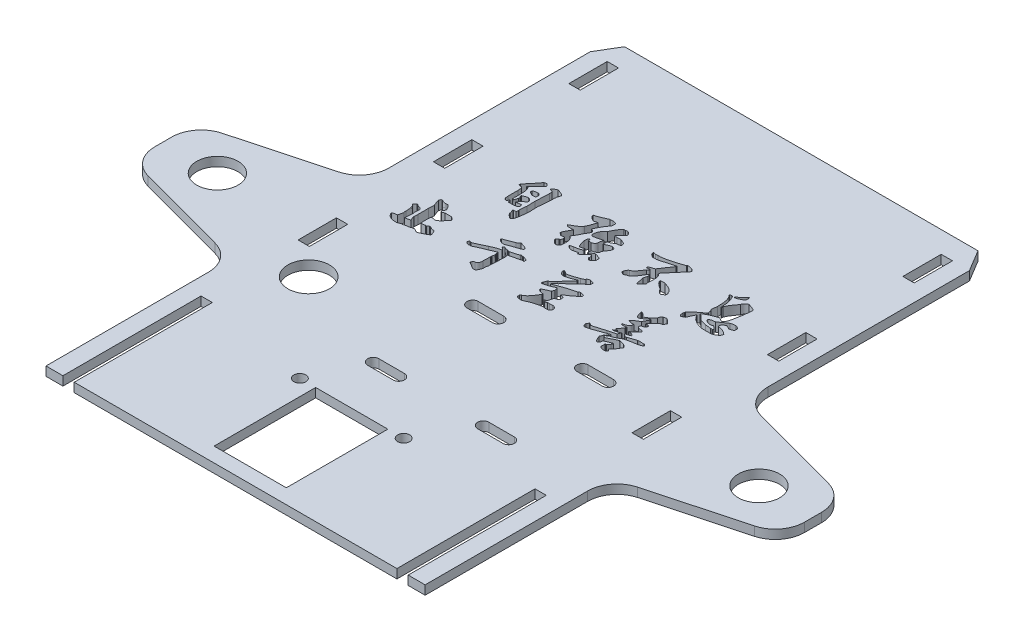
SolidWorks part; units mm, degrees
ref_plane "前视基准面" through (0, 0, 0) normal (0, 0, 1) x (1, 0, 0)
ref_plane "上视基准面" through (0, 0, 0) normal (0, 1, 0) x (1, 0, 0)
ref_plane "右视基准面" through (0, 0, 0) normal (1, 0, 0) x (0, 0, -1)
sketch "草图2" plane through (0, 0, 0) normal (0, 1, 0) x (1, 0, 0)
  line L0 (0, 0) -> (176.8067, 0) construction
  line L1 (-38.25, 19.425) -> (-38.25, 27.925)
  line L2 (-42, 62.675) -> (42, 62.675)
  line L3 (42, 62.675) -> (42, -62.675)
  line L4 (42, -62.675) -> (-42, -62.675) construction
  line L5 (-42, -62.675) -> (-42, 62.675)
  line L14 (0, 0) -> (0, 100.3728) construction
  line L15 (35.75, 57.925) -> (38.25, 57.925)
  line L16 (38.25, 57.925) -> (38.25, 49.425)
  line L17 (38.25, 49.425) -> (35.75, 49.425)
  line L18 (35.75, 49.425) -> (35.75, 57.925)
  line L19 (-38.25, 49.425) -> (-38.25, 57.925)
  line L20 (-38.25, 57.925) -> (-35.75, 57.925)
  line L21 (-35.75, 57.925) -> (-35.75, 49.425)
  line L22 (-35.75, 49.425) -> (-38.25, 49.425)
  line L23 (-38.25, 27.925) -> (-35.75, 27.925)
  line L24 (-35.75, 27.925) -> (-35.75, 19.425)
  line L25 (-35.75, 19.425) -> (-38.25, 19.425)
  line L26 (35.75, 27.925) -> (38.25, 27.925)
  line L27 (38.25, 27.925) -> (38.25, 19.425)
  line L28 (38.25, 19.425) -> (35.75, 19.425)
  line L29 (35.75, 19.425) -> (35.75, 27.925)
  line L30 (-38.25, -10.575) -> (-38.25, -2.075)
  line L31 (-38.25, -2.075) -> (-35.75, -2.075)
  line L32 (-35.75, -2.075) -> (-35.75, -10.575)
  line L33 (-35.75, -10.575) -> (-38.25, -10.575)
  line L34 (35.75, -2.075) -> (38.25, -2.075)
  line L35 (38.25, -2.075) -> (38.25, -10.575)
  line L36 (38.25, -10.575) -> (35.75, -10.575)
  line L37 (35.75, -10.575) -> (35.75, -2.075)
  line L38 (-38.25, -40.575) -> (-38.25, -32.075)
  line L39 (-38.25, -32.075) -> (-35.75, -32.075)
  line L40 (-35.75, -32.075) -> (-35.75, -40.575)
  line L41 (-35.75, -40.575) -> (-38.25, -40.575) construction
  line L42 (35.75, -32.075) -> (38.25, -32.075)
  line L43 (38.25, -32.075) -> (38.25, -40.575)
  line L44 (38.25, -40.575) -> (35.75, -40.575) construction
  line L45 (35.75, -40.575) -> (35.75, -32.075)
  line L46 (-38.25, -40.575) -> (-38.25, -60.625)
  line L47 (-38.25, -60.625) -> (-35.75, -60.625) construction
  line L48 (-35.75, -60.625) -> (-35.75, -40.575)
  line L49 (38.25, -60.625) -> (35.75, -60.625) construction
  line L50 (35.75, -40.575) -> (35.75, -60.625)
  line L51 (38.25, -40.575) -> (38.25, -60.625)
  line L52 (-38.25, -60.625) -> (-38.25, -62.675)
  line L53 (-38.25, -62.675) -> (-42, -62.675)
  line L54 (-35.75, -60.625) -> (-35.75, -62.675)
  line L55 (-35.75, -62.675) -> (35.75, -62.675)
  line L56 (35.75, -62.675) -> (35.75, -60.625)
  line L57 (38.25, -60.625) -> (38.25, -62.675)
  line L58 (38.25, -62.675) -> (42, -62.675)
  dimension "D1" = 71.5
  dimension "D2" = 2.5
  dimension "D3" = 4.75
  dimension "D4" = 8.5
  dimension "D6" = 125.35
  dimension "D7" = 2.05
  dimension "D8" = 3.75
  dimension "D5" = 4
extrude "主板和连接结构" add sketch "草图2" along normal blind 2
sketch "草图4" plane through (0, 0, 0) normal (0, 1, 0) x (1, 0, 0)
  line L0 (-38.25, -10.575) -> (-35.75, -10.575) construction
  line L1 (0, 0) -> (0, 93.7217) construction
  line L2 (-42, 8.2741) -> (-72, 0.1831)
  line L3 (-42, 62.675) -> (-42, -62.675) construction
  line L4 (-72, 0.1831) -> (-72, -13.5831)
  line L5 (-72, -13.5831) -> (-42, -21.6741)
  line L6 (-42, -21.6741) -> (-42, 8.2741)
  line L7 (-60, -6.7) -> (60, -6.7) construction
  line L8 (0, 0) -> (128.2014, 0) construction
  line L9 (72, -13.5831) -> (42, -21.6741)
  line L10 (72, 0.1831) -> (72, -13.5831)
  line L11 (42, 8.2741) -> (72, 0.1831)
  line L12 (42, -21.6741) -> (42, 8.2741)
  circle A0 centre (-60, -6.7) radius 4.575
  circle A1 centre (60, -6.7) radius 4.575
  point P15 (-72, -6.7)
  dimension "D2" = 9.15
  dimension "D1" = 3.875
  dimension "D3" = 60
  dimension "D4" = 30
extrude "天线接口-外飘" add sketch "草图4" along normal up to surface (2 mm away) up to face at (0, 2, 31.5833)
sketch "草图5" plane through (0, 0, 0) normal (0, 1, 0) x (1, 0, 0)
  line L2 (0, 0) -> (0, 101.9804) construction
  line L5 (-42, 57.925) -> (-39.15, 62.675)
  line L6 (-42, 62.675) -> (-42, 8.2741) construction
  line L7 (42, 62.675) -> (-42, 62.675) construction
  line L8 (-39.15, 62.675) -> (-42, 62.675)
  line L9 (-42, 62.675) -> (-42, 57.925)
  line L17 (42, 62.675) -> (42, 57.925)
  line L18 (39.15, 62.675) -> (42, 62.675)
  line L19 (42, 57.925) -> (39.15, 62.675)
  line L20 (-35.75, 57.925) -> (-38.25, 57.925) construction
  dimension "D1" = 2.85
extrude "美观" cut sketch "草图5" along normal through all contours L17 L8 L9 | L19 L17 L18 region at (-41.05, 0, -61.0917) region at (41.05, 0, -61.0917)
fillet "美观-2" radius 6.5 8 edges at (42, 1, 21.6741) (72, 1, 13.5831) (72, 1, -0.1831) (42, 1, -8.2741) (-42, 1, 21.6741) (-72, 1, 13.5831) (-72, 1, -0.1831) (-42, 1, -8.2741)
sketch "草图6" plane through (0, 2, 0) normal (0, 1, 0) x (1, 0, 0)
  line L0 (-35.75, 19.425) -> (35.75, 19.425) construction
  text T0 "  自强不息\r\n止于至善" font "汉呈王天喜毛笔书法" height 8.5
extrude "校训" cut sketch "草图6" against normal blind 2
sketch "草图7" plane through (0, 2, 0) normal (0, 1, 0) x (1, 0, 0)
  line L0 (0, 0) -> (0, -70.1611) construction
  line L1 (-8, -36.9295) -> (8, -36.9295)
  line L2 (-8, -36.9295) -> (-8, -59.4295)
  line L3 (-8, -59.4295) -> (8, -59.4295)
  line L4 (8, -36.9295) -> (8, -59.4295)
  line L5 (-6.5, -3.658) -> (-0.8577, -3.658) construction
  line L6 (-6.5, -2.408) -> (-0.8577, -2.408)
  line L7 (-6.5, -4.908) -> (-0.8577, -4.908)
  line L8 (-6.5, -25.658) -> (-0.8577, -25.658) construction
  line L9 (-6.5, -24.408) -> (-0.8577, -24.408)
  line L10 (-6.5, -26.908) -> (-0.8577, -26.908)
  line L11 (17.8577, -3.658) -> (23.5, -3.658) construction
  line L12 (17.8577, -2.408) -> (23.5, -2.408)
  line L13 (17.8577, -4.908) -> (23.5, -4.908)
  line L14 (17.8577, -25.658) -> (23.5, -25.658) construction
  line L15 (17.8577, -24.408) -> (23.5, -24.408)
  line L16 (17.8577, -26.908) -> (23.5, -26.908)
  line L17 (-6.5, -3.658) -> (-6.5, -25.658) construction
  circle A0 centre (-11.5, -36.9295) radius 1.325
  circle A1 centre (11.5, -36.9295) radius 1.325
  arc A2 (-6.5, -2.408) -> (-6.5, -4.908) centre (-6.5, -3.658) ccw
  arc A3 (-0.8577, -4.908) -> (-0.8577, -2.408) centre (-0.8577, -3.658) ccw
  arc A4 (-6.5, -24.408) -> (-6.5, -26.908) centre (-6.5, -25.658) ccw
  arc A5 (-0.8577, -26.908) -> (-0.8577, -24.408) centre (-0.8577, -25.658) ccw
  arc A6 (17.8577, -2.408) -> (17.8577, -4.908) centre (17.8577, -3.658) ccw
  arc A7 (23.5, -4.908) -> (23.5, -2.408) centre (23.5, -3.658) ccw
  arc A8 (17.8577, -24.408) -> (17.8577, -26.908) centre (17.8577, -25.658) ccw
  arc A9 (23.5, -26.908) -> (23.5, -24.408) centre (23.5, -25.658) ccw
  circle A10 centre (-30, -16.4771) radius 4.6
  point P12 (0, -36.9295)
  point P13 (0, -59.4295)
  point P15 (-3.6789, -3.658)
  point P20 (-3.6789, -25.658)
  point P31 (20.6789, -3.658)
  point P36 (20.6789, -25.658)
  point P45 (0, 0)
  point P46 (0, 0)
  point P47 (0, 0)
  dimension "D1" = 2.65
  dimension "D4" = 9.2
  dimension "D10" = 1.25
  dimension "D2" = 23
  dimension "D3" = 16
  dimension "D5" = 22
  dimension "D6" = 30
  dimension "D7" = 6.5
  dimension "D8" = 23.5
  dimension "D9" = 22.5
extrude "数传和UWB接口" cut sketch "草图7" against normal blind 2
